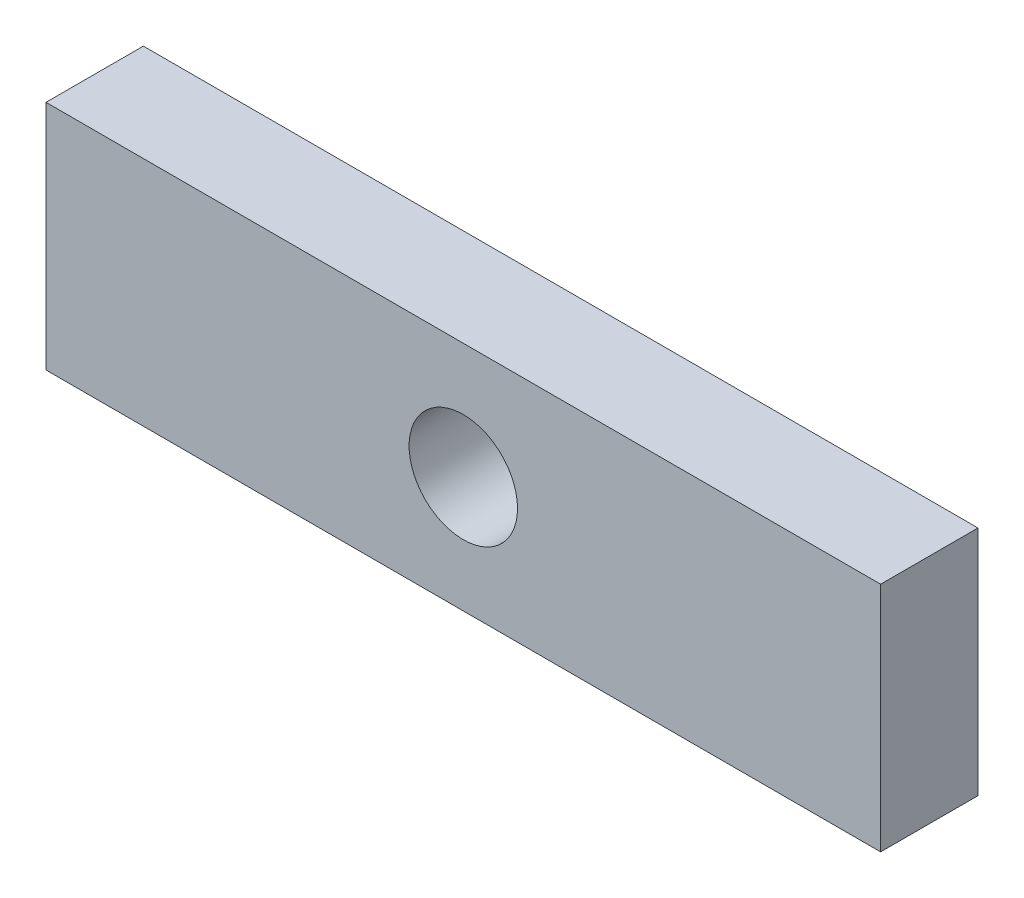
SolidWorks part; units mm, degrees
ref_plane "Front Plane" through (0, 0, 0) normal (0, 0, 1) x (1, 0, 0)
ref_plane "Top Plane" through (0, 0, 0) normal (0, 1, 0) x (1, 0, 0)
ref_plane "Right Plane" through (0, 0, 0) normal (1, 0, 0) x (0, 0, -1)
sketch "Sketch1" plane through (0, 0, 0) normal (0, 0, 1) x (1, 0, 0)
  line L1 (0, 0) -> (54, 0)
  line L2 (0, 0) -> (0, 15)
  line L3 (0, 15) -> (54, 15)
  line L4 (54, 0) -> (54, 15)
  dimension "D1" = 15
  dimension "D2" = 54
extrude "Boss-Extrude1" add sketch "Sketch1" along normal blind 6.3
sketch "Sketch2" plane through (0, 0, 6.3) normal (0, 0, 1) x (1, 0, 0)
  line L0 (0, 15) -> (0, 0) construction
  line L1 (54, 15) -> (0, 15) construction
  circle A0 centre (27, 7.5) radius 3.5081
  point P4 (0, 7.5)
  point P7 (27, 15)
extrude "Cut-Extrude1" cut sketch "Sketch2" against normal through all
